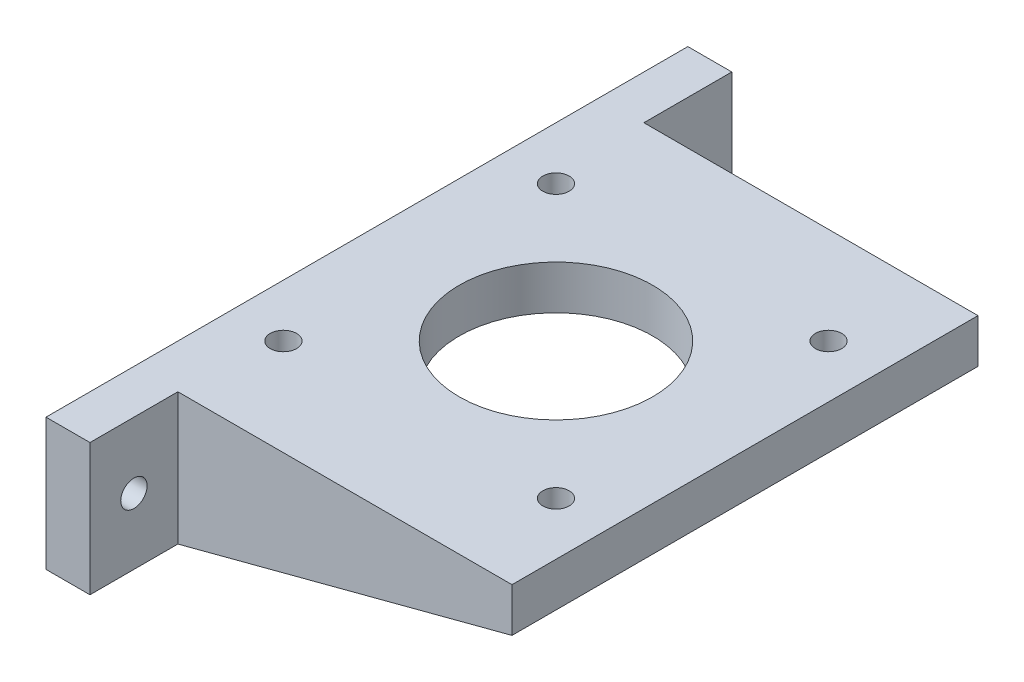
SolidWorks part; units mm, degrees
material "ABS"
ref_plane "Front Plane" through (0, 0, 0) normal (0, 0, 1) x (1, 0, 0)
ref_plane "Top Plane" through (0, 0, 0) normal (0, 1, 0) x (1, 0, 0)
ref_plane "Right Plane" through (0, 0, 0) normal (1, 0, 0) x (0, 0, -1)
sketch "Sketch1" plane through (0, 0, 0) normal (0, 0, 1) x (1, 0, 0)
  line L0 (5, 5) -> (43, 5)
  line L1 (0, 0) -> (5, 0)
  line L2 (0, 0) -> (0, 5)
  line L3 (0, 5) -> (5, 5)
  line L4 (5, 0) -> (5, 5)
  line L5 (43, 5) -> (43, 0)
  line L6 (43, 0) -> (5, 0)
  line L7 (5, 0) -> (5, -10)
  line L8 (5, -10) -> (0, -10)
  line L9 (0, -10) -> (0, 0)
  line L10 (5, -10) -> (43, 0)
  dimension "D1" = 5
  dimension "D2" = 5
  dimension "D3" = 43
  dimension "D4" = 10
extrude "Boss-Extrude1" add sketch "Sketch1" against normal blind 43 contours L1 L4 L3 L2 | L6 L5 L0 L4 region at (2.5, 2.5, 0) region at (24, 2.5, 0)
sketch "Sketch2" plane through (0, 5, 0) normal (0, 1, 0) x (1, 0, 0)
  line L3 (0, 43) -> (0, 0) construction
  line L4 (0, 0) -> (43, 0) construction
  circle A0 centre (21.5, 21.5) radius 11
  circle A1 centre (37, 37) radius 1.5
  circle A2 centre (6, 37) radius 1.5
  circle A3 centre (6, 6) radius 1.5
  circle A4 centre (37, 6) radius 1.5
  dimension "D3" = 22
  dimension "D4" = 3
  dimension "D1" = 21.5
  dimension "D2" = 21.5
  dimension "D5" = 15.5
  dimension "D6" = 15.5
  dimension "D7" = 2
  dimension "D8" = 2
extrude "Cut-Extrude1" cut sketch "Sketch2" against normal through all
extrude "Boss-Extrude2" add sketch "Sketch1<3>" along normal blind 5 contours L7 L10 L6 | L6 L5 L0 L4 | L1 L4 L3 L2 | L9 L8 L7 L1 region at (2.5, 2.5, 0) region at (24, 2.5, 0) region at (2.5, -5, 0) region at (17.6667, -3.3333, 0)
sketch "Sketch1<3>" plane through (0, 0, 0) normal (0, 0, 1) x (1, 0, 0) same geometry as "Sketch1"
extrude "Boss-Extrude3" add sketch "Sketch1<4>" against normal blind 5 from vertex contours L1 L4 L3 L2 | L9 L8 L7 L1 | L7 L10 L6 | L6 L5 L0 L4 region at (2.5, 2.5, 0) region at (24, 2.5, 0) region at (2.5, -5, 0) region at (17.6667, -3.3333, 0) starting at point (0, 5, -43)
sketch "Sketch1<4>" plane through (0, 0, 0) normal (0, 0, 1) x (1, 0, 0) same geometry as "Sketch1"
sketch "Sketch3" plane through (0, 0, 0) normal (-1, 0, 0) x (0, 0, 1)
  line L0 (5, -10) -> (0, -10) construction
  line L1 (5, 5) -> (15, 5)
  line L2 (5, 5) -> (5, -10)
  line L3 (5, -10) -> (15, -10)
  line L4 (15, 5) -> (15, -10)
  line L5 (10, 5) -> (10, -10) construction
  line L6 (15, -2.5) -> (5, -2.5) construction
  line L7 (-21.5, 5) -> (-21.5, 0) construction
  line L8 (-48, 5) -> (5, 5) construction
  line L9 (-43, 0) -> (0, 0) construction
  line L10 (-48, -10) -> (-58, -10)
  line L11 (-58, 5) -> (-58, -10)
  line L12 (-53, 5) -> (-53, -10) construction
  line L13 (-58, -2.5) -> (-48, -2.5) construction
  line L14 (-48, 5) -> (-48, -10)
  line L15 (-48, 5) -> (-58, 5)
  circle A0 centre (10, -2.5) radius 1.5
  circle A1 centre (-53, -2.5) radius 1.5
  dimension "D2" = 3
  dimension "D1" = 10
extrude "Boss-Extrude4" add sketch "Sketch3" against normal blind 5
equation "\"rod_diameter\"= 8"
equation "\"rod_hole_thickness\"= 4"
equation "\"rod_radius\"= \"rod_diameter\" / 2"
equation "\"platter_diameter\"= 320"
equation "\"platter_radius\"= \"platter_diameter\" / 2"
equation "\"extruder_mount_hole_spacing\"= 75"
equation "\"arm_rod_spacing\"= 40"
equation "\"D2@Sketch2\" = \"D1@Boss-Extrude1\" / 2"
equation "\"motor_level_rod_spacing\"= 15"
equation "\"top_frame_spacing\"= 90"
equation "\"linear_bearing_diameter\"= 15"
equation "\"z_rod_spacing\"= 75"
equation "\"platter_rod_spacing\"= 50"
equation "\"rod_nut_thickness\"= 6.5"
equation "\"rod_nut_inscribed_diameter\"= 13"
equation "\"z_height\"= 350"
equation "\"gear_pitch\"=2"
equation "\"r_gear_teeth\"= 450"
equation "\"theta_gear_teeth\"= 385"
equation "\"sheet_thickness\"=5"
equation "\"sheet_tab_hole_thickness\"= \"sheet_thickness\""
equation "\"sheet_tab_width\"= \"sheet_thickness\"*2"
equation "\"sheet_bolt_diameter\"= 3"
equation "\"sheet_bolt_length\"= 16"
equation "\"sheet_nut_diameter\"= 5.5"
equation "\"sheet_nut_thickness\"= 2.5"
equation "\"sheet_nut_depth\"= 10"
equation "\"bearing_outside_diameter\"= 22"
equation "\"bearing_thickness\"= 7"
equation "\"corner_part_thickness\"= \"sheet_thickness\" + \"bearing_thickness\""
equation "\"D4@Sketch1\"=\"sheet_thickness\"+5"
equation "\"D1@Sketch2\"= \"D3@Sketch1\" / 2"
equation "\"D1@Sketch3\"=\"sheet_thickness\"*2"
equation "\"D2@Sketch3\"=\"sheet_bolt_diameter\""
